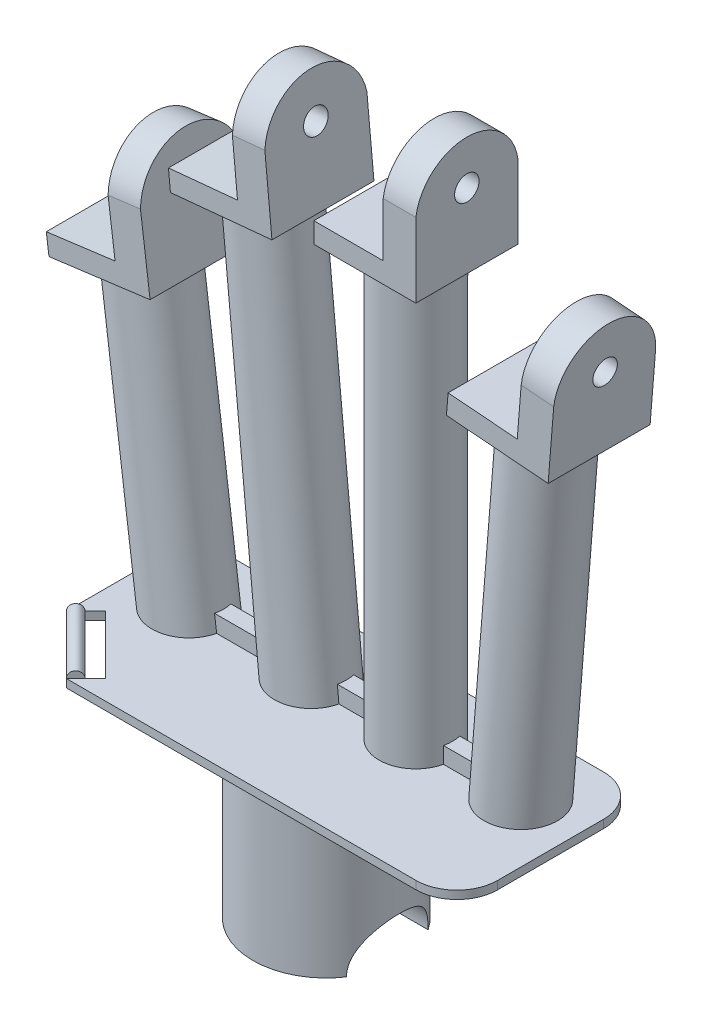
SolidWorks part; units mm, degrees
ref_plane "Front Plane" through (0, 0, 0) normal (0, 0, 1) x (1, 0, 0)
ref_plane "Top Plane" through (0, 0, 0) normal (0, 1, 0) x (1, 0, 0)
ref_plane "Right Plane" through (0, 0, 0) normal (1, 0, 0) x (0, 0, -1)
sketch "Sketch4" plane through (0, 0, 0) normal (0, 0, 1) x (1, 0, 0)
  line L0 (118.2783, 361.3249) -> (982.8327, 361.3249) construction
  line L1 (0, 0) -> (0, 70)
  line L2 (0, 70) -> (-2, 70)
  line L3 (-2, 70) -> (-2, 0)
  line L4 (-2, 0) -> (0, 0)
  line L5 (0, 0) -> (14, 0)
  line L6 (12.4732, 68.0138) -> (14.4732, 68.0138)
  line L7 (9, 0) -> (15, 0)
  line L8 (7, 0) -> (12.4732, 68.0138)
  line L10 (9, 0) -> (14.4732, 68.0138)
  line L11 (-2, 0) -> (-9, 0)
  line L12 (-9, 0) -> (-11, 0)
  line L13 (-11, 0) -> (-18, 0)
  line L14 (-18, 0) -> (-20, 0)
  line L15 (-11, 0) -> (-17.4559, 67.3971)
  line L16 (-17.4559, 67.3971) -> (-15.4559, 67.3971)
  line L17 (-15.4559, 67.3971) -> (-9, 0)
  line L18 (-18, 0) -> (-26.2108, 62.7795)
  line L19 (-26.2108, 62.7795) -> (-28.2108, 62.7795)
  line L20 (-28.2108, 62.7795) -> (-20, 0)
  line L21 (-20, 0) -> (-26, 0)
  line L22 (0, 65) -> (-20, 65)
  line L24 (0, 55) -> (20.8335, 55)
  line L26 (0, 50) -> (-31.2148, 50)
  line L27 (-26, 0) -> (15, 0)
  line L28 (-26, 0) -> (-26, -2)
  line L29 (-26, -2) -> (15, -2)
  line L30 (15, 0) -> (15, -2)
  dimension "D1" = 70
  dimension "D2" = 2
  dimension "D3" = 14
  dimension "D4" = 2
  dimension "D5" = 2
  dimension "D6" = 7
  dimension "D7" = 2
  dimension "D8" = 7
  dimension "D9" = 2
  dimension "D10" = 2
  dimension "D11" = 2
  dimension "D12" = 70
  dimension "D13" = 65
  dimension "D14" = 10
  dimension "D15" = 5
  dimension "D16" = 6
  dimension "D17" = 6
  dimension "D18" = 2
extrude "Boss-Extrude1" add sketch "Sketch4" along normal blind 2 contours L24 L8 L5 L10 | L1 L26 L3 L4 | L17 L26 L15 L12 | L18 L26 L20 L14 | L30 L7 L5 L4 L11 L12 L13 L14 L21 L28 L29 | L26 L17 L22 L15 | L26 L1 L22 L3 region at (-1, 25, 0) region at (-5.5, -1, 0) region at (-1, 57.5, 0) region at (10.213, 27.5, 0) region at (-12.3947, 25, 0) region at (-15.5079, 57.5, 0) region at (-22.2697, 25, 0)
sketch "Sketch5" plane through (0, 0, 2) normal (0, 0, 1) x (1, 0, 0)
  line L0 (7, 0) -> (11.4117, 54.8228)
  line L1 (7, 0) -> (11.426, 55) construction
  line L2 (11.4117, 54.8228) -> (21.9246, 53.9768)
  line L3 (9, 0) -> (13.3988, 54.6629)
  line L4 (9, 0) -> (13.426, 55) construction
  line L5 (-2, 0) -> (-2, 65)
  line L6 (-2, 65) -> (0, 65)
  line L7 (0, 65) -> (0, 0)
  line L8 (-9, 0) -> (-15.1979, 64.7038)
  line L9 (-15.2263, 65) -> (-9, 0) construction
  line L10 (-15.1979, 64.7038) -> (-10.585, 65.1457)
  line L11 (-24.4842, 49.5778) -> (-21.0999, 50.0204)
  line L12 (-10.585, 65.1457) -> (-20.2054, 64.2242)
  line L13 (-11, 0) -> (-17.1797, 64.514)
  line L14 (-11, 0) -> (-17.2263, 65) construction
  line L15 (-18, 0) -> (-24.4842, 49.5778)
  line L16 (-18, 0) -> (-24.5394, 50) construction
  line L17 (-21.0999, 50.0204) -> (-29.0833, 48.9763)
  line L18 (-20, 0) -> (-26.4506, 49.3206)
  line L20 (-24.4842, 55.6866) -> (-21.0999, 50.0204)
  line L23 (11.4117, 54.8228) -> (9.3756, 55.8722)
  line L25 (22.6925, 57.6139) -> (21.9246, 53.9768)
  line L26 (-10.585, 65.1457) -> (2.5876, 67.2021)
  line L27 (2.5876, 67.2021) -> (9.3756, 55.8722)
  line L28 (22.6925, 57.6139) -> (5.5245, 72.3941)
  line L29 (5.5245, 72.3941) -> (-16.3252, 68.1044)
  line L30 (-29.0833, 48.9763) -> (-29.6656, 62.8492)
  line L31 (-29.6656, 62.8492) -> (-16.3252, 68.1044)
  line L32 (-20.2054, 64.2242) -> (-24.4842, 55.6866)
  dimension "D1" = 55
  dimension "D2" = 90
  dimension "D3" = 65
  dimension "D4" = 90
  dimension "D5" = 50
  dimension "D6" = 90
extrude "Cut-Extrude4" cut sketch "Sketch5" against normal blind 10 contours L32 L12 L16 L14 L13 L10 L26 L27 L23 L3 L1 L2 L25 L28 L29 L31 L30 L17 L20 L18 L11 | L3 L2 L26 L1 | L12 L13 L14 L16 | L17 L18 L20 region at (10.6564, 55.8573, 2)
sketch "Sketch6" plane through (0, 0, 2) normal (0, 0, 1) x (1, 0, 0)
  line L0 (-24.4842, 49.5778) -> (-22.6038, 35.2002)
  line L1 (-18, 0) -> (-24.4842, 49.5778) construction
  line L2 (-15.1979, 64.7038) -> (-13.8153, 50.2699)
  line L3 (-15.1979, 64.7038) -> (-9, 0) construction
  line L4 (-2, 65) -> (-2, 50.5)
  line L5 (-2, 65) -> (-2, 0) construction
  line L6 (11.4117, 54.8228) -> (10.2486, 40.3695)
  line L7 (7, 0) -> (11.4117, 54.8228) construction
  line L8 (10.2486, 40.3695) -> (13.4056, 40.1154)
  line L9 (13.4056, 40.1154) -> (14.5687, 54.5687)
  line L10 (14.5687, 54.5687) -> (11.4117, 54.8228)
  line L11 (-2, 50.5) -> (0, 50.5)
  line L12 (0, 0) -> (0, 65) construction
  line L13 (0, 50.5) -> (0, 65)
  line L14 (0, 65) -> (-2, 65)
  line L15 (-15.1979, 64.7038) -> (-17.1797, 64.514)
  line L16 (-17.1797, 64.514) -> (-15.8153, 50.2699)
  line L17 (-11, 0) -> (-17.1797, 64.514) construction
  line L18 (-13.8153, 50.2699) -> (-15.7971, 50.0801)
  line L19 (-15.7971, 50.0801) -> (-16.1419, 53.6796)
  line L20 (-22.6038, 35.2002) -> (-24.5702, 34.943)
  line L21 (-26.4506, 49.3206) -> (-20, 0) construction
  line L22 (-24.5702, 34.943) -> (-26.4506, 49.3206)
  line L23 (-26.4506, 49.3206) -> (-24.4842, 49.5778)
  line L24 (-24.5702, 34.943) -> (-22.6038, 35.2002)
  line L25 (-24.4842, 49.5778) -> (-26.4506, 49.3206)
  line L26 (-24.5702, 34.943) -> (-26.4506, 49.3206)
  line M5 (-9, 0) -> (-15.1979, 64.7038)
  line M6 (-15.1979, 64.7038) -> (-17.1797, 64.514)
  line M7 (-17.1797, 64.514) -> (-11, 0)
  line M9 (-18, 0) -> (-24.4842, 49.5778)
  line M10 (-24.4842, 49.5778) -> (-26.4506, 49.3206)
  line M11 (-26.4506, 49.3206) -> (-20, 0)
  line M17 (9, 0) -> (13.3988, 54.6629)
  line M18 (13.3988, 54.6629) -> (11.4117, 54.8228)
  line M19 (11.4117, 54.8228) -> (7, 0)
  line M21 (0, 0) -> (0, 65)
  line M22 (0, 65) -> (-2, 65)
  line M23 (-2, 65) -> (-2, 0)
  dimension "D1" = 14.5
  dimension "D2" = 14.5
  dimension "D3" = 14.5
  dimension "D4" = 14.5
extrude "Cut-Extrude5" cut sketch "Sketch6" against normal blind 10 contours L8 M19 M17 M18 | L11 M23 M21 M22 | L18 L16 M5 M6 M7 | L20 M9 M10 M11 region at (-24.5272, 42.2604, 2) region at (-15.4975, 57.3919, 2) region at (-1, 57.75, 2) region at (11.8237, 47.5162, 2)
sketch "Sketch7" plane through (0, 50.5, 0) normal (0, 1, 0) x (1, 0, 0)
  line L0 (-1, 0) -> (-1, -2)
  line L1 (-2, 0) -> (0, 0) construction
  line L2 (-2, -2) -> (0, -2) construction
  line L5 (-7.25, 5.25) -> (5.25, 5.25)
  line L6 (-7.25, 5.25) -> (-7.25, -7.25)
  line L7 (-7.25, -7.25) -> (5.25, -7.25)
  line L8 (5.25, 5.25) -> (5.25, -7.25)
  line L9 (-7.25, 5.25) -> (5.25, -7.25) construction
  line L10 (-7.25, -7.25) -> (5.25, 5.25) construction
  point P7 (-1, -1)
  line M3 (-2, 0) -> (-2, -2)
  line M4 (-2, -2) -> (0, -2)
  line M5 (0, -2) -> (0, 0)
  line M6 (0, 0) -> (-2, 0)
  dimension "D1" = 12.5
  dimension "D2" = 12.5
extrude "Boss-Extrude2" add sketch "Sketch7" along normal blind 2.5 contours L8 L5 L6 L7 M3 M6 M5 M4 | L0 M6 M3 M4 | L0 M6 M4 M5 region at (-0.5, 50.5, 1) region at (-1.5, 50.5, 1) region at (-1, 50.5, -5.0732)
sketch "Sketch8" plane through (3.2936, 40.9292, 0) normal (0.0802, 0.9968, 0) x (0.9968, -0.0802, 0)
  line L0 (12.9774, 0) -> (10.9774, 0)
  line L1 (6.9774, 0) -> (12.9774, 0)
  line L2 (6.9774, 0) -> (6.9774, -2)
  line L3 (6.9774, -2) -> (12.9774, -2)
  line L4 (12.9774, 0) -> (12.9774, -2)
  line L5 (10.9774, 0) -> (10.9774, -2)
  dimension "D1" = 6
  dimension "D2" = 2
extrude "Boss-Extrude3" add sketch "Sketch8" against normal blind 41.5 contours L0 L5 L3 L4 region at (15.2325, 39.9684, 1)
sketch "Sketch9" plane through (0, 0, 2) normal (0, 0, 1) x (1, 0, 0)
  line L0 (7, 0) -> (9, 0)
  line L1 (9, 0) -> (12.2357, 40.2096)
  line L2 (12.2357, 40.2096) -> (10.2486, 40.3695)
  line L3 (10.2486, 40.3695) -> (7, 0)
extrude "Cut-Extrude6" cut sketch "Sketch9" against normal blind 41.5
sketch "Sketch10" plane through (-4.8971, 51.1242, 0) normal (-0.0954, 0.9954, 0) x (0.9954, 0.0954, 0)
  line L0 (-14.959, -2) -> (-12.959, -2)
  line L1 (-8.959, 0) -> (-14.959, 0)
  line L2 (-8.959, 0) -> (-8.959, -2)
  line L3 (-8.959, -2) -> (-14.959, -2)
  line L4 (-14.959, 0) -> (-14.959, -2)
  line L5 (-12.959, -2) -> (-12.959, 0)
  dimension "D1" = 6
  dimension "D2" = 2
extrude "Boss-Extrude4" add sketch "Sketch10" against normal blind 50.5 contours L0 L5 L1 L4 region at (-18.7925, 49.7931, 1)
sketch "Sketch11" plane through (0, 0, 2) normal (0, 0, 1) x (1, 0, 0)
  line L0 (-11, 0) -> (-9, 0)
  line L1 (-9, 0) -> (-13.8153, 50.2699)
  line L2 (-13.8153, 50.2699) -> (-15.7971, 50.0801)
  line L3 (-15.7971, 50.0801) -> (-11, 0)
extrude "Cut-Extrude7" cut sketch "Sketch11" against normal blind 50.5
sketch "Sketch12" plane through (3.2936, 40.9292, 0) normal (0.0802, 0.9968, 0) x (0.9968, -0.0802, 0)
  line L0 (11.9774, 0) -> (11.9774, -2)
  line L1 (12.9774, 0) -> (10.9774, 0) construction
  line L2 (10.9774, -2) -> (12.9774, -2) construction
  line L4 (5.7274, 5.25) -> (18.2274, 5.25)
  line L5 (5.7274, 5.25) -> (5.7274, -7.25)
  line L6 (5.7274, -7.25) -> (18.2274, -7.25)
  line L7 (18.2274, 5.25) -> (18.2274, -7.25)
  line L8 (5.7274, 5.25) -> (18.2274, -7.25) construction
  line L9 (5.7274, -7.25) -> (18.2274, 5.25) construction
  point P6 (11.9774, -1)
  line M3 (12.9774, 0) -> (10.9774, 0)
  line M4 (10.9774, 0) -> (10.9774, -2)
  line M5 (10.9774, -2) -> (12.9774, -2)
  line M6 (12.9774, -2) -> (12.9774, 0)
  dimension "D1" = 12.5
  dimension "D2" = 12.5
extrude "Boss-Extrude5" add sketch "Sketch12" along normal blind 2.5 contours L7 L4 L5 L6 M3 M6 M5 M4 | L0 M3 M5 M6 | L0 M3 M4 M5 region at (15.7309, 39.9283, 1) region at (14.7341, 40.0085, 1) region at (15.2325, 39.9684, -5.0732)
sketch "Sketch13" plane through (0, 0, 2) normal (0, 0, 1) x (1, 0, 0)
  line L0 (-5.5, -2) -> (-5.5, 50.5)
  line L1 (-26, -2) -> (15, -2) construction
  line L2 (-7.25, 50.5) -> (5.25, 50.5) construction
  line L3 (-17.7971, 49.8885) -> (-17.6064, 47.8976)
  line L4 (-13.0183, 0) -> (-17.7971, 49.8885) construction
  line L5 (-19.788, 49.6978) -> (-19.6155, 47.8976)
  line L6 (-15.0275, 0) -> (-19.788, 49.6978) construction
  line L7 (-19.788, 49.6978) -> (-17.7971, 49.8885)
  line L8 (-17.6064, 47.8976) -> (-19.5973, 47.7069)
  line L9 (-19.5973, 47.7069) -> (-19.6379, 48.1311)
  line M3 (-13.0183, 0) -> (-17.7971, 49.8885)
  line M4 (-17.7971, 49.8885) -> (-19.788, 49.6978)
  line M5 (-19.788, 49.6978) -> (-15.0275, 0)
  dimension "D1" = 2
extrude "Cut-Extrude8" cut sketch "Sketch13" against normal blind 2.5 and the other way through all contours L8 L5 M3 M4 M5 region at (-18.6972, 48.7977, 2)
sketch "Sketch14" plane through (-4.7064, 49.1333, 0) normal (-0.0954, 0.9954, 0) x (0.9954, 0.0954, 0)
  line L0 (-13.959, 0) -> (-13.959, -2)
  line L1 (-14.959, 0) -> (-12.959, 0) construction
  line L2 (-14.959, -2) -> (-12.959, -2) construction
  line L4 (-20.209, 5.25) -> (-7.709, 5.25)
  line L5 (-20.209, 5.25) -> (-20.209, -7.25)
  line L6 (-20.209, -7.25) -> (-7.709, -7.25)
  line L7 (-7.709, 5.25) -> (-7.709, -7.25)
  line L8 (-20.209, 5.25) -> (-7.709, -7.25) construction
  line L9 (-20.209, -7.25) -> (-7.709, 5.25) construction
  point P6 (-13.959, -1)
  line M3 (-14.959, -2) -> (-12.959, -2)
  line M4 (-12.959, -2) -> (-12.959, 0)
  line M5 (-12.959, 0) -> (-14.959, 0)
  line M6 (-14.959, 0) -> (-14.959, -2)
  dimension "D1" = 12.5
  dimension "D2" = 12.5
extrude "Boss-Extrude6" add sketch "Sketch14" along normal blind 2.5 contours L0 M5 M3 M4 | L0 M5 M6 M3 | L7 L4 L5 L6 M3 M6 M5 M4 region at (-18.1041, 47.8499, 1) region at (-19.0995, 47.7546, 1) region at (-18.6018, 47.8022, -5.0732)
sketch "Sketch15" plane through (-4.9065, 37.5148, 0) normal (-0.1297, 0.9916, 0) x (0.9916, 0.1297, 0)
  line L0 (-25.848, -2) -> (-23.848, -2)
  line L1 (-17.848, 0) -> (-25.848, 0)
  line L2 (-17.848, 0) -> (-17.848, -2)
  line L3 (-17.848, -2) -> (-25.848, -2)
  line L4 (-25.848, 0) -> (-25.848, -2)
  line L5 (-23.848, -2) -> (-23.848, 0)
  line L6 (-31.848, -2) -> (-29.848, -2)
  line L7 (-25.848, 0) -> (-31.848, 0)
  line L8 (-25.848, 0) -> (-25.848, -2)
  line L9 (-25.848, -2) -> (-31.848, -2)
  line L10 (-31.848, 0) -> (-31.848, -2)
  line L11 (-29.848, -2) -> (-29.848, 0)
  dimension "D1" = 8
  dimension "D2" = 2
  dimension "D3" = 6
  dimension "D4" = 2
extrude "Boss-Extrude7" add sketch "Sketch15" against normal blind 39.5 separate body contours L6 L11 L7 L10 region at (-35.494, 33.5143, 1)
sketch "Sketch16" plane through (-4.9065, 37.5148, 0) normal (-0.1297, 0.9916, 0) x (0.9916, 0.1297, 0)
  line L0 (-30.848, 0) -> (-30.848, -2)
  line L1 (-29.848, 0) -> (-31.848, 0) construction
  line L2 (-31.848, -2) -> (-29.848, -2) construction
  line L4 (-37.098, 5.25) -> (-24.598, 5.25)
  line L5 (-37.098, 5.25) -> (-37.098, -7.25)
  line L6 (-37.098, -7.25) -> (-24.598, -7.25)
  line L7 (-24.598, 5.25) -> (-24.598, -7.25)
  line L8 (-37.098, 5.25) -> (-24.598, -7.25) construction
  line L9 (-37.098, -7.25) -> (-24.598, 5.25) construction
  point P6 (-30.848, -1)
  line M3 (-31.848, -2) -> (-29.848, -2)
  line M4 (-29.848, -2) -> (-29.848, 0)
  line M5 (-29.848, 0) -> (-31.848, 0)
  line M6 (-31.848, 0) -> (-31.848, -2)
  dimension "D1" = 12.5
  dimension "D2" = 12.5
extrude "Boss-Extrude8" add sketch "Sketch16" along normal blind 2.5 contours L7 L4 L5 L6 M3 M6 M5 M4 | L0 M5 M3 M4 | L0 M5 M6 M3 region at (-34.9982, 33.5792, 1) region at (-35.9898, 33.4495, 1) region at (-35.494, 33.5143, -5.0732)
sketch "Sketch17" plane through (-5.2307, 39.9937, 0) normal (-0.1297, 0.9916, 0) x (0.9916, 0.1297, 0)
  line L0 (-37.098, -7.25) -> (-35.098, -7.25)
  line L1 (-37.098, 5.25) -> (-22.598, 5.25)
  line L2 (-37.098, 5.25) -> (-37.098, -7.25)
  line L3 (-37.098, -7.25) -> (-22.598, -7.25)
  line L4 (-22.598, 5.25) -> (-22.598, -7.25)
  line L5 (-35.098, -7.25) -> (-35.098, 5.25)
  line M2 (-24.598, -7.25) -> (-24.598, 5.25)
  dimension "D1" = 14.5
  dimension "D2" = 2
extrude "Boss-Extrude9" add sketch "Sketch17" against normal blind 2.5 contours L4 L1 L3 M2 region at (-28.6294, 36.9334, 1)
sketch "Sketch18" plane through (-5.2307, 39.9937, 0) normal (-0.1297, 0.9916, 0) x (0.9916, 0.1297, 0)
  line L0 (-37.098, -7.25) -> (-35.098, -7.25)
  line L2 (-35.098, -7.25) -> (-37.098, -7.25)
  line L3 (-35.098, -7.25) -> (-35.098, 5.25)
  line L4 (-35.098, 5.25) -> (-37.098, 5.25)
  line L5 (-37.098, -7.25) -> (-37.098, 5.25)
  line M2 (-37.098, -7.25) -> (-22.598, -7.25)
  line M4 (-22.598, 5.25) -> (-37.098, 5.25)
  line M5 (-37.098, 5.25) -> (-37.098, -7.25)
  dimension "D1" = 2
extrude "Cut-Extrude9" cut sketch "Sketch18" against normal blind 13.5 contours L3 M2 M4 M5 region at (-41.0239, 35.3124, 1)
sketch "Sketch19" plane through (-26, 0, 0) normal (-1, 0, 0) x (0, 0, 1)
  line L1 (0, 0) -> (2, 0)
  line L2 (0, 0) -> (0, -2)
  line L3 (0, -2) -> (2, -2)
  line L4 (2, 0) -> (2, -2)
extrude "Boss-Extrude10" add sketch "Sketch19" along normal blind 7.5
sketch "Sketch20" plane through (0, 0, 2) normal (0, 0, 1) x (1, 0, 0)
  line L0 (-31.8577, -2) -> (-29.8406, -2)
  line L1 (-29.8406, -2) -> (-29.3799, -5.5224)
  line L2 (-29.3799, -5.5224) -> (-31.363, -5.7818)
  line L3 (-31.363, -5.7818) -> (-31.8577, -2)
  line L4 (-20, 0) -> (-18, 0)
  line L5 (-18, 0) -> (-22.6038, 35.2002)
  line L6 (-22.6038, 35.2002) -> (-24.5702, 34.943)
  line L7 (-24.5702, 34.943) -> (-20, 0)
extrude "Cut-Extrude11" cut sketch "Sketch20" against normal blind 33.5
sketch "Sketch21" plane through (0, 0, 2) normal (0, 0, 1) x (1, 0, 0)
  line L0 (-36.4856, 33.3846) -> (-34.5025, 33.644)
  line L1 (-34.5025, 33.644) -> (-30.1022, 0)
  line L2 (-30.1022, 0) -> (-32.1192, 0)
  line L3 (-32.1192, 0) -> (-36.4856, 33.3846)
extrude "Cut-Extrude12" cut sketch "Sketch21" against normal blind 33.5
sketch "Sketch22" plane through (-4.9065, 37.5148, 0) normal (0.1297, -0.9916, 0) x (-0.9916, -0.1297, 0)
  line L0 (28.848, -7.25) -> (28.848, 5.25)
  line L1 (35.098, -7.25) -> (22.598, -7.25) construction
  line L2 (35.098, 5.25) -> (22.598, 5.25) construction
  line L3 (28.848, -1) -> (27.848, -1)
  line L4 (28.848, -1) -> (29.848, -1)
  line L5 (28.848, -1) -> (28.848, -2)
  line L6 (28.848, -1) -> (28.848, 0)
  line L8 (29.848, -1) -> (27.848, -1)
  line L9 (29.848, -1) -> (29.848, -2)
  line L10 (29.848, -2) -> (27.848, -2)
  line L11 (27.848, -1) -> (27.848, -2)
  line L12 (27.848, -1) -> (29.848, -1)
  line L13 (27.848, -1) -> (27.848, 0)
  line L14 (27.848, 0) -> (29.848, 0)
  line L15 (29.848, -1) -> (29.848, 0)
  dimension "D1" = 1
  dimension "D2" = 1
  dimension "D3" = 1
  dimension "D4" = 1
extrude "Boss-Extrude11" add sketch "Sketch22" along normal blind 35.5 contours L4 L15 L14 L0 | L10 L9 L4 L0 | L3 L11 L10 L0 | L14 L13 L3 L0 region at (-33.0151, 33.8385, 1.5) region at (-34.0067, 33.7088, 1.5) region at (-33.0151, 33.8385, 0.5) region at (-34.0067, 33.7088, 0.5)
sketch "Sketch24" plane through (18.1687, -1.4621, 0) normal (0.9968, -0.0802, 0) x (0, 0, -1)
  line L0 (-1, 41.0615) -> (-1, 55.5615)
  line L1 (5.25, 41.0615) -> (-7.25, 41.0615) construction
  line L2 (-1.7404, 43.5615) -> (-1.7404, 55.5615)
  line L3 (-7.25, 41.0615) -> (-1, 41.0615)
  line L4 (-7.25, 41.0615) -> (-7.25, 55.5615)
  line L6 (-1, 41.0615) -> (-1, 55.5615)
  line L8 (-1, 55.5615) -> (-1, 41.0615)
  line L9 (-1, 41.0615) -> (5.25, 41.0615)
  line L10 (5.25, 55.5615) -> (5.25, 41.0615)
  line L11 (5.25, 43.5615) -> (-7.25, 43.5615) construction
  line L12 (-7.25, 49.5615) -> (5.25, 49.5615)
  arc A1 (-7.25, 49.5615) -> (5.25, 49.5615) centre (-1, 49.282) cw
  point P17 (-1, 49.5615)
  line M4 (5.25, 43.5615) -> (-7.25, 43.5615)
  dimension "D1" = 14.5
extrude "Boss-Extrude13" add sketch "Sketch24" against normal blind 4 contours A1 L8 L12 | A1 L2 L12 L8 | A1 L12 L2 | L12 L4 L2 M4 | L12 L0 L10 M4 | L12 L2 L0 M4 region at (21.9035, 44.9494, 1.3702) region at (21.9035, 44.9494, -2.125) region at (22.3833, 50.9112, 1.3698) region at (22.3469, 50.459, -1.6268) region at (21.9035, 44.9494, 4.4952) region at (22.3404, 50.3778, 4.0322)
sketch "Sketch25" plane through (5.25, 0, 0) normal (1, 0, 0) x (0, 0, -1)
  line L0 (-1, 50.5) -> (-1, 65)
  line L1 (5.25, 50.5) -> (-7.25, 50.5) construction
  line L3 (-1, 65) -> (-7.25, 65)
  line L4 (-1, 65) -> (-1, 50.5)
  line L5 (-1, 50.5) -> (-7.25, 50.5)
  line L6 (-7.25, 65) -> (-7.25, 50.5)
  line L7 (-1, 65) -> (5.25, 65)
  line L8 (-1, 65) -> (-1, 50.5)
  line L9 (-1, 50.5) -> (5.25, 50.5)
  line L10 (5.25, 65) -> (5.25, 50.5)
  arc A0 (5.25, 57.75) -> (-7.25, 57.75) centre (-1, 58.681) ccw
  line M4 (5.25, 53) -> (-7.25, 53)
  dimension "D1" = 14.5
extrude "Boss-Extrude14" add sketch "Sketch25" against normal blind 4 contours L10 A0 L0 M4 | L0 A0 L6 M4 region at (5.25, 58.4301, 3.915) region at (5.25, 58.4301, -1.915)
sketch "Sketch26" plane through (-7.6739, -0.7351, 0) normal (0.9954, 0.0954, 0) x (0, 0, -1)
  line L0 (-1, 49.3582) -> (-1, 63.8582)
  line L1 (5.25, 49.3582) -> (-7.25, 49.3582) construction
  line L3 (-1, 63.8582) -> (-7.25, 63.8582)
  line L4 (-1, 63.8582) -> (-1, 49.3582)
  line L5 (-1, 49.3582) -> (-7.25, 49.3582)
  line L6 (-7.25, 63.8582) -> (-7.25, 49.3582)
  line L7 (-1, 63.8582) -> (5.25, 63.8582)
  line L8 (-1, 63.8582) -> (-1, 49.3582)
  line L9 (-1, 49.3582) -> (5.25, 49.3582)
  line L10 (5.25, 63.8582) -> (5.25, 49.3582)
  arc A0 (5.25, 56.6082) -> (-7.25, 56.6082) centre (-1, 57.5392) ccw
  line M4 (5.25, 51.8582) -> (-7.25, 51.8582)
  dimension "D1" = 14.5
extrude "Boss-Extrude15" add sketch "Sketch26" against normal blind 4 contours L10 A0 L0 M4 | L0 A0 L6 M4 region at (-13.1365, 56.2922, 3.915) region at (-13.1365, 56.2922, -1.915)
sketch "Sketch27" plane through (-22.4072, -2.9306, 0) normal (0.9916, 0.1297, 0) x (0, 0, -1)
  line L0 (-1, 37.8343) -> (-1, 52.3343)
  line L1 (5.25, 37.8343) -> (-7.25, 37.8343) construction
  line L3 (-1, 52.3343) -> (5.25, 52.3343)
  line L4 (-1, 52.3343) -> (-1, 37.8343)
  line L5 (-1, 37.8343) -> (5.25, 37.8343)
  line L6 (5.25, 52.3343) -> (5.25, 37.8343)
  line L7 (-1, 52.3343) -> (-7.25, 52.3343)
  line L8 (-1, 52.3343) -> (-1, 37.8343)
  line L9 (-1, 37.8343) -> (-7.25, 37.8343)
  line L10 (-7.25, 52.3343) -> (-7.25, 37.8343)
  arc A0 (5.25, 45.0843) -> (-7.25, 45.0843) centre (-1, 46.0153) ccw
  line M2 (5.25, 40.3343) -> (-7.25, 40.3343)
  dimension "D1" = 14.5
extrude "Boss-Extrude16" add sketch "Sketch27" against normal blind 4 contours L6 A0 L0 M2 | L0 A0 L10 M2 region at (-28.3421, 42.4474, 3.915) region at (-28.3421, 42.4474, -1.915)
sketch "Sketch28" plane through (0, 50.5, 0) normal (0, -1, 0) x (-1, 0, 0)
  line L0 (1, -2) -> (1, -7.25)
  line L1 (2, -2) -> (0, -2) construction
  line L2 (7.25, -7.25) -> (-5.25, -7.25) construction
  line L3 (1, -7.25) -> (1, 5.25)
  line L4 (7.25, 5.25) -> (-5.25, 5.25) construction
  circle A0 centre (1, -1) radius 4.5
  line M1 (2, 0) -> (2, -2)
  line M2 (2, -2) -> (0, -2)
  line M3 (0, -2) -> (0, 0)
  line M4 (0, 0) -> (2, 0)
  dimension "D1" = 9
extrude "Boss-Extrude17" add sketch "Sketch28" along normal blind 57 contours L3 A0 L0 M2 M3 M4 | L0 A0 L3 M4 M1 M2 region at (-3.0045, 50.5, 1) region at (1.0045, 50.5, 1)
sketch "Sketch29" plane through (-4.7064, 49.1333, 0) normal (0.0954, -0.9954, 0) x (-0.9954, -0.0954, 0)
  line L0 (13.959, -7.25) -> (13.959, 5.25)
  line L1 (20.209, -7.25) -> (7.709, -7.25) construction
  line L2 (20.209, 5.25) -> (7.709, 5.25) construction
  circle A0 centre (13.959, -1) radius 4.5
  line M1 (14.959, 0) -> (14.959, -2)
  line M2 (14.959, -2) -> (12.959, -2)
  line M3 (12.959, -2) -> (12.959, 0)
  line M4 (12.959, 0) -> (14.959, 0)
  dimension "D1" = 9
extrude "Boss-Extrude18" add sketch "Sketch29" along normal blind 57 contours L0 A0 M4 M1 M2 | L0 A0 M2 M3 M4 region at (-16.6065, 47.9934, 1) region at (-20.5971, 47.6111, 1)
sketch "Sketch30" plane through (-4.9065, 37.5148, 0) normal (0.1297, -0.9916, 0) x (0.9916, 0.1297, 0)
  line L0 (-28.848, 7.25) -> (-28.848, -5.25)
  line L1 (-35.098, 7.25) -> (-22.598, 7.25) construction
  line L2 (-35.098, -5.25) -> (-22.598, -5.25) construction
  circle A0 centre (-28.848, 1) radius 4.5
  line M1 (-27.848, 2) -> (-27.848, 0)
  line M2 (-27.848, 0) -> (-29.848, 0)
  line M3 (-29.848, 0) -> (-29.848, 2)
  line M4 (-29.848, 2) -> (-27.848, 2)
  dimension "D1" = 9
extrude "Boss-Extrude19" add sketch "Sketch30" along normal blind 57 contours L0 A0 M2 M3 M4 | L0 A0 M4 M1 M2 region at (-31.5234, 34.0336, 1) region at (-35.4984, 33.5137, 1)
sketch "Sketch31" plane through (3.2936, 40.9292, 0) normal (-0.0802, -0.9968, 0) x (-0.9968, 0.0802, 0)
  line L0 (-11.9774, -7.25) -> (-11.9774, 5.25)
  line L1 (-5.7274, -7.25) -> (-18.2274, -7.25) construction
  line L2 (-5.7274, 5.25) -> (-18.2274, 5.25) construction
  circle A0 centre (-11.9774, -1) radius 4.5
  line M5 (-10.9774, -2) -> (-12.9774, -2)
  line M6 (-12.9774, -2) -> (-12.9774, 0)
  line M7 (-12.9774, 0) -> (-10.9774, 0)
  line M8 (-10.9774, 0) -> (-10.9774, -2)
  dimension "D1" = 9
extrude "Boss-Extrude20" add sketch "Sketch31" along normal blind 57 contours L0 A0 M7 M8 M5 | L0 A0 M5 M6 M7 region at (17.2305, 39.8077, 1) region at (13.2345, 40.1292, 1)
sketch "Sketch32" plane through (0, -2, 0) normal (0, -1, 0) x (1, 0, 0)
  line L1 (-81.5094, 22.199) -> (41.4502, 22.199)
  line L2 (-81.5094, 22.199) -> (-81.5094, -20.6146)
  line L3 (-81.5094, -20.6146) -> (41.4502, -20.6146)
  line L4 (41.4502, 22.199) -> (41.4502, -20.6146)
  line L5 (-81.5094, 22.199) -> (41.4502, -20.6146) construction
  line L6 (-81.5094, -20.6146) -> (41.4502, 22.199) construction
  point P0 (-20.0296, 0.7922)
extrude "Cut-Extrude13" cut sketch "Sketch32" along normal blind 57
sketch "Sketch33" plane through (0, -2, 0) normal (0, -1, 0) x (-1, 0, 0)
  line L0 (24.4073, 0) -> (-7.4536, 0)
  line L1 (-7.4536, -2) -> (24.4073, -2)
  line L2 (8.4769, -2) -> (8.4769, 0)
  line L4 (30.9769, -9) -> (-14.0231, -9)
  line L5 (35.9769, -4) -> (35.9769, 2)
  line L6 (30.9769, 7) -> (-14.0231, 7)
  line L7 (-19.0231, -4) -> (-19.0231, 2)
  line L8 (35.9769, -9) -> (-19.0231, 7) construction
  line L9 (35.9769, 7) -> (-19.0231, -9) construction
  arc A0 (-19.0231, -4) -> (-14.0231, -9) centre (-14.0231, -4) ccw
  arc A1 (35.9769, -4) -> (30.9769, -9) centre (30.9769, -4) cw
  arc A2 (35.9769, 2) -> (30.9769, 7) centre (30.9769, 2) ccw
  arc A3 (-19.0231, 2) -> (-14.0231, 7) centre (-14.0231, 2) cw
  point P10 (8.4769, -1)
  line M1 (-3.3875, 0) -> (-7.4536, 0)
  ellipse M2 centre (-11.8552, -1) end of major axis (-16.3698, -1) minor radius 4.5 (-7.4536, 0) -> (-7.4536, -2) ccw
  line M3 (-7.4536, -2) -> (-3.3875, -2)
  arc M4 (-3.3875, -2) -> (5.3875, -2) centre (1, -1) ccw
  line M5 (5.3875, -2) -> (9.4237, -2)
  ellipse M6 centre (13.8313, -1) end of major axis (18.3519, -1) minor radius 4.5 (9.4237, -2) -> (18.2389, -2) ccw
  line M7 (18.2389, -2) -> (24.4073, -2)
  ellipse M8 centre (28.8321, -1) end of major axis (33.3704, -1) minor radius 4.5 (24.4073, -2) -> (33.257, -2) ccw
  line M9 (33.257, -2) -> (33.5, -2)
  line M10 (33.5, -2) -> (33.5, 0)
  line M11 (33.5, 0) -> (33.257, 0)
  ellipse M12 centre (28.8321, -1) end of major axis (33.3704, -1) minor radius 4.5 (33.257, 0) -> (24.4073, 0) ccw
  line M13 (24.4073, 0) -> (18.2389, 0)
  ellipse M14 centre (13.8313, -1) end of major axis (18.3519, -1) minor radius 4.5 (18.2389, 0) -> (9.4237, 0) ccw
  line M15 (9.4237, 0) -> (5.3875, 0)
  arc M16 (5.3875, 0) -> (-3.3875, 0) centre (1, -1) ccw
  dimension "D3" = 5
  dimension "D1" = 55
  dimension "D2" = 16
extrude "Boss-Extrude21" add sketch "Sketch33" along normal blind 1 contours A3 L7 A0 L4 A1 L5 A2 L6 L0 L1 M1 M16 M15 M14 M13 M12 M11 M10 M9 M8 M7 M6 M5 M4 M3 M2 | L2 L0 L1 M5 M1 M2 M3 | L2 L1 L0 M7 M8 M9 M10 M11 M12 M13 M15 | L1 M6 | L0 M14 | L0 M16 | L1 M4 region at (-24.7515, -2, 1) region at (-13.8313, -2, -1.4604) region at (7.7175, -2, 1) region at (-1, -2, -1.4606) region at (-1, -2, 3.4606) region at (-13.8313, -2, 3.4604) region at (-8.4769, -2, 8.4272)
sketch "Sketch34" plane through (-26.3734, -3.4493, 0) normal (-0.9916, -0.1297, 0) x (0, 0, 1)
  line L0 (1, 40.3343) -> (1, 46.9343)
  line L1 (-5.25, 40.3343) -> (7.25, 40.3343) construction
  circle A0 centre (1, 46.9343) radius 1.5
  dimension "D2" = 3
  dimension "D1" = 6.6
extrude "Cut-Extrude14" cut sketch "Sketch34" against normal blind 8 contours A0 region at (-32.3264, 42.0667, 2.0307)
sketch "Sketch35" plane through (-11.6556, -1.1165, 0) normal (-0.9954, -0.0954, 0) x (0, 0, 1)
  line L0 (1, 51.8582) -> (1, 58.4582)
  line L1 (-5.25, 51.8582) -> (7.25, 51.8582) construction
  circle A0 centre (1, 58.4582) radius 1.5
  dimension "D2" = 3
  dimension "D1" = 6.6
extrude "Cut-Extrude15" cut sketch "Sketch35" against normal blind 8 contours A0 region at (-17.1315, 56.0494, 2.0307)
sketch "Sketch36" plane through (1.25, 0, 0) normal (-1, 0, 0) x (0, 0, 1)
  line L0 (1, 53) -> (1, 59.6)
  line L1 (-5.25, 53) -> (7.25, 53) construction
  circle A0 centre (1, 59.6) radius 1.5
  dimension "D2" = 3
  dimension "D1" = 6.6
extrude "Cut-Extrude16" cut sketch "Sketch36" against normal blind 8 contours A0 region at (1.25, 58.5693, 2.0307)
sketch "Sketch37" plane through (14.1816, -1.1412, 0) normal (-0.9968, 0.0802, 0) x (0, 0, 1)
  line L0 (1, 43.5615) -> (1, 50.1615)
  line L1 (-5.25, 43.5615) -> (7.25, 43.5615) construction
  circle A0 centre (1, 50.1615) radius 1.5
  dimension "D2" = 3
  dimension "D1" = 6.6
extrude "Cut-Extrude17" cut sketch "Sketch37" against normal blind 8 contours A0 region at (18.1225, 47.8313, 2.0307)
sketch "Sketch38" plane through (0, -3, 0) normal (0, -1, 0) x (-1, 0, 0)
  line L0 (-19.0231, -4) -> (-19.0231, 2) construction
  line L1 (-19.0231, -1) -> (7.4808, -1)
  line L2 (-19.0231, -1) -> (-19.0231, -11)
  line L3 (-14.0231, -16) -> (7.4808, -16)
  line L4 (7.4808, -1) -> (7.4808, -16)
  line L5 (35.9769, -4) -> (35.9769, 2) construction
  line L6 (35.9769, -1) -> (7.4808, -1)
  line L7 (35.9769, -1) -> (35.9769, -11)
  line L8 (30.9769, -16) -> (7.4808, -16)
  line L9 (7.4808, -1) -> (7.4808, -16)
  arc A0 (30.9769, -16) -> (35.9769, -11) centre (30.9769, -11) ccw
  arc A1 (-14.0231, -16) -> (-19.0231, -11) centre (-14.0231, -11) cw
  point P14 (-19.0231, -16)
  arc M4 (-19.0231, -4) -> (-14.0231, -9) centre (-14.0231, -4) ccw
  line M5 (-14.0231, -9) -> (30.9769, -9)
  arc M6 (30.9769, -9) -> (35.9769, -4) centre (30.9769, -4) ccw
  dimension "D2" = 5
  dimension "D1" = 15
extrude "Boss-Extrude22" add sketch "Sketch38" against normal blind 1 contours A1 L3 L4 L2 M5 M4 | L8 A0 L7 L4 M6 M5 region at (5.7712, -3, 12.2976) region at (-21.7288, -3, 12.3117)
sketch "Sketch39" plane through (0, -2, 0) normal (0, 1, 0) x (1, 0, 0)
  line L0 (-34.5124, -14.5355) -> (-30.093, -18.955)
  line L1 (-38.9318, -10.1161) -> (-30.093, -18.955)
  line L2 (-38.9318, -10.1161) -> (-47.7706, -18.955)
  line L3 (-47.7706, -18.955) -> (-39.1652, -28.0271)
  line L4 (-39.1652, -28.0271) -> (-30.093, -18.955)
  arc A0 (-35.9769, -11) -> (-30.9769, -16) centre (-30.9769, -11) ccw construction
  point P7 (-34.5124, -14.5355)
  dimension "D1" = 6.25
  dimension "D2" = 12.5
extrude "Boss-Extrude23" add sketch "Sketch39" along normal blind 2 and the other way blind 2 separate body contours L3 L4 L0 L1 L2 region at (-38.9712, -2, 19.0327)
sketch "Sketch40" plane through (0, 0, 0) normal (0, 1, 0) x (1, 0, 0)
  line L0 (-38.9318, -10.1161) -> (-50.2455, -21.4298)
  line L1 (-30.093, -18.955) -> (-41.4067, -30.2687)
  line L2 (-38.9318, -10.1161) -> (-35.9769, -8.8888)
  line L3 (-35.9769, -11) -> (-35.9769, 2) construction
  line L4 (-35.9769, -8.8888) -> (-30.1971, -14.6685)
  line L5 (-35.9769, -8.8888) -> (-28.8656, -16)
  line L6 (14.0231, -16) -> (-30.9769, -16) construction
  line L7 (-28.8656, -16) -> (-30.093, -18.955)
  line L8 (-50.2455, -21.4298) -> (-41.4067, -30.2687)
  line M4 (-47.7706, -18.955) -> (-39.1652, -28.0271)
  line M6 (-30.093, -18.955) -> (-38.9318, -10.1161)
  dimension "D1" = 16
  dimension "D2" = 16
  dimension "D3" = 90
extrude "Boss-Extrude24" add sketch "Sketch40" against normal blind 4 contours L7 L5 L4 L2 M6 | L0 L8 L1 M4 region at (-33.5046, 0, 13.5277) region at (-44.7189, 0, 24.5963)
sketch "Sketch41" plane through (0, -2, 0) normal (0, 1, 0) x (1, 0, 0)
  line L0 (-41.4067, -30.2687) -> (-32.5678, -21.4298)
  line L1 (-41.4067, -30.2687) -> (-30.093, -18.955) construction
  line L2 (-50.2455, -21.4298) -> (-41.4067, -12.591)
  line L3 (-38.9318, -10.1161) -> (-50.2455, -21.4298) construction
  line L4 (-41.4067, -12.591) -> (-32.5678, -21.4298)
  line L5 (-50.2455, -21.4298) -> (-41.4067, -30.2687)
  line L6 (-32.5678, -21.4298) -> (-35.3963, -18.6014)
  line L7 (-35.3963, -18.6014) -> (-44.2351, -27.4402)
  dimension "D1" = 12.5
  dimension "D2" = 12.5
  dimension "D3" = 4
extrude "Boss-Extrude25" add sketch "Sketch41" along normal blind 12.5 contours L4 L7 L5 L0 region at (-38.4015, -2, 24.435)
sketch "Sketch42" plane through (-8.3974, 0, -8.3974) normal (-0.7071, 0, -0.7071) x (-0.7071, 0, 0.7071)
  line L0 (50.6821, 10.5) -> (50.6821, 0) construction
  line L1 (38.1821, 10.5) -> (38.1821, 0) construction
  arc A0 (50.6821, 5.25) -> (38.1821, 5.25) centre (44.4321, 4.1548) ccw
  arc A1 (38.1821, 5.25) -> (50.6821, 5.25) centre (44.4321, 9.3395) cw
extrude "Cut-Extrude18" cut sketch "Sketch42" against normal blind 12.5
sketch "Sketch43" plane through (-14.4078, 0, -14.4078) normal (-0.7071, 0, -0.7071) x (-0.7071, 0, 0.7071)
  line L0 (50.6821, -4) -> (50.6821, 0)
  line L3 (50.6821, -2) -> (34.6821, -2)
  line L4 (50.6821, -2) -> (50.6821, 0)
  line L5 (50.6821, 0) -> (34.6821, 0)
  line L6 (34.6821, -2) -> (34.6821, 0)
  point P3 (50.6821, -2)
  line M3 (50.6821, 0) -> (34.6821, 0)
  line M4 (34.6821, 0) -> (34.6821, -4)
extrude "Cut-Extrude19" cut sketch "Sketch43" against normal blind 8.5 contours L3 L0 M3 M4 region at (-44.5887, -1, 15.773)
sketch "Sketch44" plane through (-8.3974, 0, -8.3974) normal (-0.7071, 0, -0.7071) x (-0.7071, 0, 0.7071)
  line L0 (44.4321, 10.5) -> (44.4321, -2)
  line L1 (50.6821, -2) -> (34.6821, -2) construction
  line L2 (44.4321, -2) -> (44.4321, 4.6)
  arc A0 (50.6821, 5.25) -> (38.1821, 5.25) centre (44.4321, 4.1548) ccw construction
  circle A1 centre (44.4321, 4.6) radius 1.5
  dimension "D2" = 3
  dimension "D1" = 6.6
extrude "Cut-Extrude20" cut sketch "Sketch44" against normal blind 8.5 contours L0 A1 | L0 A1 region at (-40.2658, 4.6, 23.471) region at (-39.3655, 4.6, 22.5707)
sketch "Sketch45" plane through (0, -3, 0) normal (0, -1, 0) x (-1, 0, 0)
  line L0 (7.4212, -16) -> (7.4212, 7)
  line L1 (-14.0231, -16) -> (28.8656, -16) construction
  line L2 (30.9769, 7) -> (-14.0231, 7) construction
  line L3 (8.4769, 7) -> (8.4769, -16)
  circle A0 centre (8.4769, -4.5) radius 9
  dimension "D1" = 18
extrude "Boss-Extrude27" add sketch "Sketch45" along normal blind 20 contours L0 A0 | L3 A0 L0 | L3 A0 region at (-4.0807, -3, 4.5) region at (-7.9496, -3, 4.5) region at (-12.2966, -3, 4.5)
sketch "Sketch46" plane through (0, 0, 0) normal (0, 0, 1) x (1, 0, 0)
  line L3 (-8.4769, -45.8264) -> (-8.4769, -89.2893)
  arc A1 (-8.4769, -45.8264) -> (-8.4769, -89.2893) centre (-8.4769, -67.5578) cw
revolve "Revolve1" add sketch "Sketch46" angle 360 about L3
sketch "Sketch47" plane through (0, -23, 0) normal (0, -1, 0) x (-1, 0, 0)
  circle A0 centre (8.4769, -4.5) radius 9
sketch "Sketch50" plane through (0, 0, 0) normal (0, 1, 0) x (1, 0, 0)
  line L0 (-8.4769, 21.7314) -> (-8.4769, -21.7314)
  circle A0 centre (-8.4769, 0) radius 21.7314 construction
  circle A1 centre (-8.4769, 0) radius 9
  dimension "D1" = 18
extrude "Cut-Extrude23" cut sketch "Sketch50" against normal blind 65 from offset 30 contours L0 A1 | L0 A1 region at (-4.6571, 0, 0) region at (-12.2966, 0, 0) offset against normal yes
sketch "Sketch52" plane through (0, 0, 0) normal (1, 0, 0) x (0, 0, -1)
  line L0 (0, -47.7777) -> (0, -87.338)
  line L1 (9, -47.7777) -> (-9, -47.7777) construction
  line L2 (-9, -87.338) -> (9, -87.338) construction
  line L3 (0, -87.338) -> (0, -67.5578)
  line L5 (10.1618, -87.338) -> (-10.1618, -87.338)
  line L6 (10.1618, -87.338) -> (10.1618, -47.7777)
  line L7 (10.1618, -47.7777) -> (-10.1618, -47.7777)
  line L8 (-10.1618, -87.338) -> (-10.1618, -47.7777)
  line L9 (10.1618, -87.338) -> (-10.1618, -47.7777) construction
  line L10 (10.1618, -47.7777) -> (-10.1618, -87.338) construction
  line L11 (28.3288, -45.1895) -> (-28.3288, -45.1895)
  line L12 (28.3288, -45.1895) -> (28.3288, -89.9262)
  line L13 (28.3288, -89.9262) -> (-28.3288, -89.9262)
  line L14 (-28.3288, -45.1895) -> (-28.3288, -89.9262)
  line L15 (28.3288, -45.1895) -> (-28.3288, -89.9262) construction
  line L16 (28.3288, -89.9262) -> (-28.3288, -45.1895) construction
extrude "Cut-Extrude24" cut sketch "Sketch52" against normal blind 65 and the other way blind 65 contours L11 L14 L13 L12 L5 L8 L7 L6 region at (0, -67.5578, -27.6069)
sketch "Sketch53" plane through (0, 0, 0) normal (0, 1, 0) x (1, 0, 0)
  line L1 (-8.8004, -28.9281) -> (-8.8004, -72.3881)
  arc A3 (-8.8004, -72.3881) -> (-8.8004, -28.9281) centre (-8.8004, -50.6581) cw
revolve "Revolve2" add sketch "Sketch53" angle 360 about L1
sketch "Sketch54" plane through (0, 0, 0) normal (0, 1, 0) x (1, 0, 0)
  line L0 (-8.8004, -72.3881) -> (-8.8004, -49.9784)
  line L1 (-8.8004, -72.3881) -> (1.3596, -72.3881)
  line L2 (-20.1024, -72.3881) -> (2.5017, -72.3881)
  line L3 (-20.1024, -72.3881) -> (-20.1024, -28.9281)
  line L4 (-20.1024, -28.9281) -> (2.5017, -28.9281)
  line L5 (2.5017, -72.3881) -> (2.5017, -28.9281)
  line L6 (-20.1024, -72.3881) -> (2.5017, -28.9281) construction
  line L7 (-20.1024, -28.9281) -> (2.5017, -72.3881) construction
  line L8 (-18.9604, -72.3881) -> (1.3596, -72.3881)
  line L10 (1.3596, -72.3881) -> (-18.9604, -72.3881)
  line L11 (1.3596, -72.3881) -> (1.3596, -28.9281)
  line L12 (1.3596, -28.9281) -> (-18.9604, -28.9281)
  line L13 (-18.9604, -72.3881) -> (-18.9604, -28.9281)
  circle A0 centre (-8.8004, -50.6581) radius 21.73 construction
  circle A1 centre (-8.8004, -50.6581) radius 21.73
  point P14 (-8.8004, -72.3881)
  dimension "D1" = 22.6041
  dimension "D2" = 10.16
extrude "Cut-Extrude25" cut sketch "Sketch54" against normal blind 65 and the other way blind 65 contours L11 A1 L13 region at (-13.9189, 0, 71.2826)
sketch "Sketch55" plane through (0, 0, 0) normal (0, 0, 1) x (1, 0, 0)
  line L2 (67.524, -43.8258) -> (67.524, -0.3658)
  arc A3 (67.524, -0.3658) -> (67.524, -43.8258) centre (67.524, -22.0958) ccw
revolve "Revolve3" add sketch "Sketch55" angle 360 about L2
sketch "Sketch56" plane through (0, 0, 0) normal (0, 0, 1) x (1, 0, 0)
  circle A0 centre (67.524, -22.0958) radius 5
  circle A1 centre (67.524, -22.0958) radius 43.6141
  dimension "D1" = 10
extrude "Cut-Extrude26" cut sketch "Sketch56" against normal blind 65 and the other way blind 65
sketch "Sketch57" plane through (0, 0, 10.1618) normal (0, 0, 1) x (1, 0, 0)
  circle A0 centre (-8.4769, -67.5578) radius 5
  dimension "D1" = 10
extrude "Cut-Extrude27" cut sketch "Sketch57" against normal blind 65
sketch "Sketch58" plane through (0, 0, 0) normal (1, 0, 0) x (0, 0, -1)
  circle A0 centre (-50.6581, 0) radius 5
  dimension "D1" = 10
extrude "Cut-Extrude28" cut sketch "Sketch58" against normal blind 38 and the other way blind 17
sketch "Sketch59" plane through (0, 0, 10.1618) normal (0, 0, 1) x (1, 0, 0)
  line L0 (-8.4769, -67.5578) -> (10.7323, -67.5578)
  line L1 (-8.4769, -67.5578) -> (-27.686, -67.5578)
  line L2 (-14.7269, -61.3078) -> (-2.2269, -61.3078)
  line L3 (-14.7269, -61.3078) -> (-14.7269, -73.8078)
  line L4 (-14.7269, -73.8078) -> (-2.2269, -73.8078)
  line L5 (-2.2269, -61.3078) -> (-2.2269, -73.8078)
  line L6 (-14.7269, -61.3078) -> (-2.2269, -73.8078) construction
  line L7 (-14.7269, -73.8078) -> (-2.2269, -61.3078) construction
  line L8 (23.0587, -67.5578) -> (-40.0124, -67.5578)
  line L9 (-40.0124, -40.1199) -> (23.0587, -40.1199)
  line L10 (-40.0124, -40.1199) -> (-40.0124, -94.9958)
  line L11 (-40.0124, -94.9958) -> (23.0587, -94.9958)
  line L12 (23.0587, -40.1199) -> (23.0587, -94.9958)
  line L13 (-40.0124, -40.1199) -> (23.0587, -94.9958) construction
  line L14 (-40.0124, -94.9958) -> (23.0587, -40.1199) construction
  circle A0 centre (-8.4769, -67.5578) radius 19.2092 construction
  circle M4 centre (-8.4769, -67.5578) radius 19.2092
  dimension "D1" = 12.5
  dimension "D2" = 12.5
extrude "Cut-Extrude29" cut sketch "Sketch59" against normal blind 38 contours L12 L8 L10 L11 M4 | L0 L5 L4 L3 L1 M4 region at (-8.4769, -76.4937, 10.1618) region at (16.8955, -68.2457, 10.1618)
sketch "Sketch60" plane through (-18.9604, 0, 0) normal (1, 0, 0) x (0, 0, -1)
  line L0 (-50.6581, -5) -> (-50.6581, 5)
  line L1 (-26.7055, 0) -> (-74.6107, 0)
  line L2 (-26.7055, 24.8261) -> (-74.6107, 24.8261)
  line L3 (-56.9081, 6.25) -> (-44.4081, 6.25)
  line L4 (-56.9081, 6.25) -> (-56.9081, -6.25)
  line L5 (-56.9081, -6.25) -> (-44.4081, -6.25)
  line L6 (-44.4081, 6.25) -> (-44.4081, -6.25)
  line L7 (-56.9081, 6.25) -> (-44.4081, -6.25) construction
  line L8 (-56.9081, -6.25) -> (-44.4081, 6.25) construction
  line L9 (-26.7055, 24.8261) -> (-26.7055, -24.8261)
  line L10 (-26.7055, -24.8261) -> (-74.6107, -24.8261)
  line L11 (-74.6107, 24.8261) -> (-74.6107, -24.8261)
  line L12 (-26.7055, 24.8261) -> (-74.6107, -24.8261) construction
  line L13 (-26.7055, -24.8261) -> (-74.6107, 24.8261) construction
  circle A1 centre (-50.6581, 0) radius 5 construction
  point P7 (-50.6581, 0)
  point P8 (-50.6581, 0)
  point P18 (-50.6581, 0)
  circle M4 centre (-50.6581, 0) radius 19.2085
  dimension "D1" = 12.5
  dimension "D2" = 12.5
extrude "Cut-Extrude30" cut sketch "Sketch60" against normal blind 38 and the other way blind 38 contours L1 L6 L5 L4 M4 | L1 L11 L10 L9 M4 region at (-18.9604, -12.413, 27.245) region at (-18.9604, -8.9356, 50.6581)
sketch "Sketch61" plane through (0, 0, 0) normal (0, 0, 1) x (1, 0, 0)
  line L1 (-56.142, 69.5548) -> (36.856, 69.5548)
  line L2 (-56.142, 69.5548) -> (-56.142, -34.6971)
  line L3 (-56.142, -34.6971) -> (36.856, -34.6971)
  line L4 (36.856, 69.5548) -> (36.856, -34.6971)
  line L5 (36.856, 69.5548) -> (88.781, 69.5548)
  line L6 (36.856, 69.5548) -> (36.856, -60.2112)
  line L7 (36.856, -60.2112) -> (88.781, -60.2112)
  line L8 (88.781, 69.5548) -> (88.781, -60.2112)
  line L9 (-56.142, -34.6971) -> (31.1223, -34.6971)
  line L10 (-56.142, -34.6971) -> (-56.142, -105.6449)
  line L11 (-56.142, -105.6449) -> (31.1223, -105.6449)
  line L12 (31.1223, -34.6971) -> (31.1223, -105.6449)
extrude "Cut-Extrude31" cut sketch "Sketch61" against normal blind 38 and the other way blind 38 contours L12 L3 L10 L11 | L8 L5 L4 L6 L7 region at (62.8185, 4.6718, 0) region at (-12.5099, -70.171, 0)
sketch "Sketch62" plane through (0, 0, 0) normal (1, 0, 0) x (0, 0, -1)
  line L0 (-30.8234, 25.549) -> (-30.8234, -22.0717)
  line L1 (-31.6562, 13.9887) -> (-76.5535, 13.9887)
  line L2 (-31.6562, 13.9887) -> (-31.6562, -22.0717)
  line L3 (-31.6562, -22.0717) -> (-76.5535, -22.0717)
  line L4 (-76.5535, 13.9887) -> (-76.5535, -22.0717)
  line L5 (-29.9347, 25.549) -> (-76.5535, 25.549)
  line L6 (-29.9347, 25.549) -> (-29.9347, -22.0717)
  line L7 (-29.9347, -22.0717) -> (-76.5535, -22.0717)
  line L8 (-76.5535, 25.549) -> (-76.5535, -22.0717)
extrude "Cut-Extrude32" cut sketch "Sketch62" against normal blind 38 and the other way blind 38 contours L1 L4 L3 L2 | L5 L8 L1 L2 L7 L0 region at (0, 18.4889, 52.4816) region at (0, -4.0415, 54.1048)
sketch "Sketch63" plane through (1.3596, 0, 0) normal (-1, 0, 0) x (0, 0, 1)
  line L1 (26.0198, 27.674) -> (75.7981, 27.674)
  line L2 (26.0198, 27.674) -> (26.0198, -9.8751)
  line L3 (26.0198, -9.8751) -> (75.7981, -9.8751)
  line L4 (75.7981, 27.674) -> (75.7981, -9.8751)
  line L5 (26.0198, 27.674) -> (75.7981, -9.8751) construction
  line L6 (26.0198, -9.8751) -> (75.7981, 27.674) construction
  point P0 (50.9089, 8.8995)
extrude "Cut-Extrude33" cut sketch "Sketch63" against normal blind 38
sketch "Sketch64" plane through (0, 0, 0) normal (1, 0, 0) x (0, 0, -1)
  line L0 (-13.5, -23) -> (4.5, -23) construction
  circle A0 centre (-4.5, -23) radius 5
  dimension "D1" = 10
extrude "Cut-Extrude34" cut sketch "Sketch64" against normal blind 23 and the other way blind 10
sketch "Sketch65" plane through (-5.569, 0, -5.569) normal (0.7071, 0, 0.7071) x (0.7071, 0, -0.7071)
  line L0 (-30.1945, 0) -> (-30.1945, -4)
  line L1 (-34.6821, 0) -> (-46.61, 0)
  line L2 (-34.6821, 0) -> (-34.6821, -11.133)
  line L3 (-34.6821, -11.133) -> (-46.61, -11.133)
  line L4 (-46.61, 0) -> (-46.61, -11.133)
  line L5 (-34.6821, -4) -> (-28.4775, -4)
  line L6 (-34.6821, -4) -> (-34.6821, 0)
  line L7 (-34.6821, 0) -> (-28.4775, 0)
  line L8 (-28.4775, -4) -> (-28.4775, 0)
  circle A0 centre (-30.1945, -2) radius 0.8089
  line M6 (-34.6821, -4) -> (-34.6821, 0)
extrude "Boss-Extrude28" add sketch "Sketch65" against normal blind 10.1 from offset 1.2 contours A0 L0 L7 L5 M6 region at (-28.588, -2, 17.4499) offset against normal yes
sketch "Sketch66" plane through (-13.5593, 0, -13.5593) normal (-0.7071, 0, -0.7071) x (-0.7071, 0, 0.7071)
  line L0 (30.1945, 0) -> (30.1945, -4)
  line L1 (31.7771, 0) -> (28.7771, 0)
  line L2 (31.7771, 0) -> (31.7771, -4)
  line L3 (31.7771, -4) -> (28.7771, -4)
  line L4 (28.7771, 0) -> (28.7771, -4)
  line L5 (30.1945, -1.1911) -> (30.1945, 0)
  line L6 (30.1945, -2.8606) -> (30.1945, -4)
  line L7 (30.1945, 0) -> (30.1945, -1.1911)
  line L8 (30.1945, -0.5955) -> (31.7771, -0.5955)
  line L9 (30.1945, -4) -> (30.1945, -2.8606)
  line L10 (30.1945, -3.4303) -> (31.7771, -3.4303)
  arc A1 (30.1945, -3.4303) -> (30.1945, -0.5955) centre (30.1945, -2.0129) cw
  circle A2 centre (30.1945, -2.0129) radius 0.8219
  line M3 (30.1945, -3) -> (30.1945, -4)
  dimension "D1" = 3
extrude "Boss-Extrude30" add sketch "Sketch66" against normal blind 10.1 contours A2 L7 A1 L0 M3 region at (-34.8876, -0.8933, 7.769)
sketch "Sketch67" plane through (-13.5593, 0, -13.5593) normal (-0.7071, 0, -0.7071) x (-0.7071, 0, 0.7071)
  line L0 (31.7771, -4) -> (31.7771, 0) construction
  line L1 (31.0034, -2) -> (31.7771, -2)
  line L2 (31.0034, -2) -> (31.0034, -3.2798)
  line L3 (31.0034, -3.2798) -> (31.7771, -3.2798)
  line L4 (31.7771, -2) -> (31.7771, -3.2798)
extrude "Cut-Extrude35" cut sketch "Sketch67" along normal blind 10.1
sketch "Sketch68" plane through (0, 0, 0) normal (0, 1, 0) x (1, 0, 0)
  line L0 (-17.4769, -4.5) -> (-8.4769, -4.5)
  line L2 (-9.9769, -6) -> (-6.9769, -6)
  line L3 (-9.9769, -6) -> (-9.9769, -3)
  line L4 (-9.9769, -3) -> (-6.9769, -3)
  line L5 (-6.9769, -6) -> (-6.9769, -3)
  line L6 (-9.9769, -6) -> (-6.9769, -3) construction
  line L7 (-9.9769, -3) -> (-6.9769, -6) construction
  arc A0 (-15.9602, 0.5) -> (-15.9602, -9.5) centre (-8.4769, -4.5) ccw construction
  dimension "D1" = 3
  dimension "D2" = 3
extrude "Cut-Extrude38" cut sketch "Sketch68" against normal blind 6 and the other way blind 6 from offset 20 contours L2 L5 L4 L3 region at (-9.9344, 0, 5.25) offset against normal yes
sketch "Sketch70" plane through (0, -2, 0) normal (0, 1, 0) x (1, 0, 0)
  line L0 (-26.766, -13.931) -> (-28.8351, -16)
  line L3 (-33.9078, -6.7892) -> (-35.482, -8.3634)
  line L4 (-35.482, -8.3634) -> (-35.9769, -7.8685)
  line L9 (-26.766, -13.931) -> (-33.9078, -6.7892)
  arc A0 (-28.8351, -16) -> (-35.482, -8.3634) centre (-41.4918, -20.3054) cw
  line M10 (-26.766, -13.931) -> (-27.1872, -14.3521)
  line M11 (-27.1872, -14.3521) -> (-34.3289, -7.2103)
  line M12 (-34.3289, -7.2103) -> (-33.9078, -6.7892)
  line M13 (-33.9078, -6.7892) -> (-26.766, -13.931)
  line M31 (-35.482, -8.3634) -> (-28.3402, -15.5052)
  line M32 (-28.3402, -15.5052) -> (-28.8351, -16)
extrude "Cut-Extrude44" cut sketch "Sketch70" against normal blind 28 and the other way blind 28 contours L3 L0 M11 M31 | M10 M13 M12 M11 | A0 M32 M31 region at (-30.5475, -2, 10.5706) region at (-31.3346, -2, 11.3577) region at (-41.5415, -2, 20.3627)
sketch "Sketch73" plane through (-6.4175, 0, -6.4175) normal (-0.7071, 0, -0.7071) x (-0.7071, 0, 0.7071)
  line L0 (31.7032, -2) -> (30.0732, -2)
  line L1 (28.7771, -2) -> (31.7032, -2) construction
  circle A0 centre (30.8882, -2) radius 0.815
  line M6 (31.7032, -2) -> (28.7771, -2)
  dimension "D1" = 1.63
extrude "Boss-Extrude31" add sketch "Sketch73" along normal blind 10.1 contours A0 M6 | A0 M6 region at (-28.2588, -2.3459, 15.4237) region at (-28.2588, -1.6541, 15.4237)
sketch "Sketch74" plane through (0, -2, 0) normal (0, 1, 0) x (1, 0, 0)
  line L0 (-34.8243, -7.7056) -> (-33.587, -6.4684)
  line L1 (-33.587, -6.4684) -> (-26.2533, -13.8022)
  line L2 (-27.6825, -14.8474) -> (-26.4453, -13.6102)
  line L3 (-27.6825, -14.8474) -> (-34.8243, -7.7056)
  line M1 (-33.9078, -6.7892) -> (-26.766, -13.931)
extrude "Cut-Extrude45" cut sketch "Sketch74" against normal blind 10.1 contours L2 L1 L0 M1 region at (-30.1765, -2, 10.1997)
sketch "Sketch75" plane through (0, 0, 0) normal (0, 1, 0) x (1, 0, 0)
  line L0 (-9.5023, -1) -> (-5.5, -1)
  arc A0 (-5.3875, 0) -> (-5.3875, -2) centre (-1, -1) ccw construction
  ellipse E0 centre (-14.0229, -1) end of major axis (-18.5435, -1) minor radius 4.5 (-9.6153, -2) -> (-9.6153, 0) ccw construction
